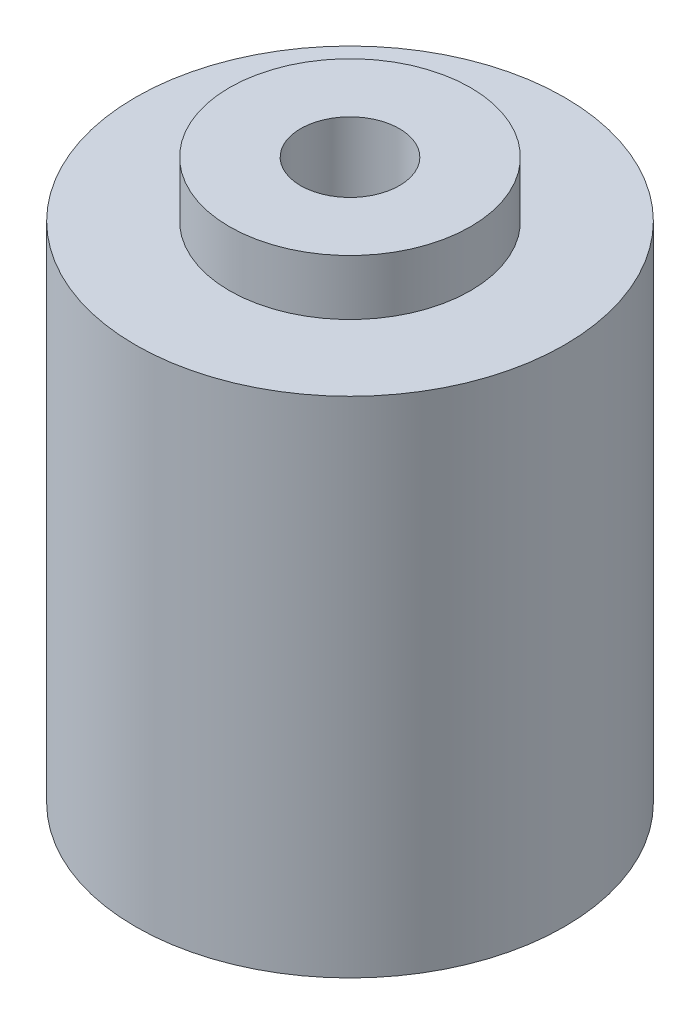
SolidWorks part; units mm, degrees
ref_plane "Alzado" through (0, 0, 0) normal (0, 0, 1) x (1, 0, 0)
ref_plane "Planta" through (0, 0, 0) normal (0, 1, 0) x (1, 0, 0)
ref_plane "Vista lateral" through (0, 0, 0) normal (1, 0, 0) x (0, 0, -1)
sketch "Croquis1" plane through (0, 0, 0) normal (0, 1, 0) x (1, 0, 0)
  circle A0 centre (0, 0) radius 22.606
  dimension "D1" = 45.212
extrude "Saliente-Extruir1" add sketch "Croquis1" along normal blind 50.8
sketch "Croquis2" plane through (0, 0, 0) normal (0, 1, 0) x (1, 0, 0)
  circle A0 centre (0, 0) radius 12.7
  dimension "D1" = 25.4
extrude "Saliente-Extruir2" add sketch "Croquis2" along normal blind 56.642
sketch "Croquis3" plane through (0, 0, 0) normal (1, 0, 0) x (0, 0, -1)
  circle A0 centre (0, 40.0328) radius 2.54
  circle A1 centre (0, 15.4281) radius 2.54
  dimension "D1" = 5.08
  dimension "D2" = 5.08
extrude "Cortar-Extruir1" cut sketch "Croquis3" against normal blind 31.242
sketch "Croquis4" plane through (0, 0, 0) normal (0, 1, 0) x (1, 0, 0)
  circle A0 centre (0, 0) radius 5.207
  dimension "D1" = 10.414
extrude "Cortar-Extruir4" cut sketch "Croquis4" along normal blind 144.018
sketch "Croquis5" plane through (0, 0, 0) normal (0, 1, 0) x (1, 0, 0)
  circle A0 centre (0, 0) radius 22.606
extrude "Saliente-Extruir3" add sketch "Croquis5" against normal blind 2.286
dome "Cúpula1" faces to dome 1 distance 2.54 reverse direction no elliptical dome no face at (0, -2.286, 22.606) parameters "D1"=2.54
